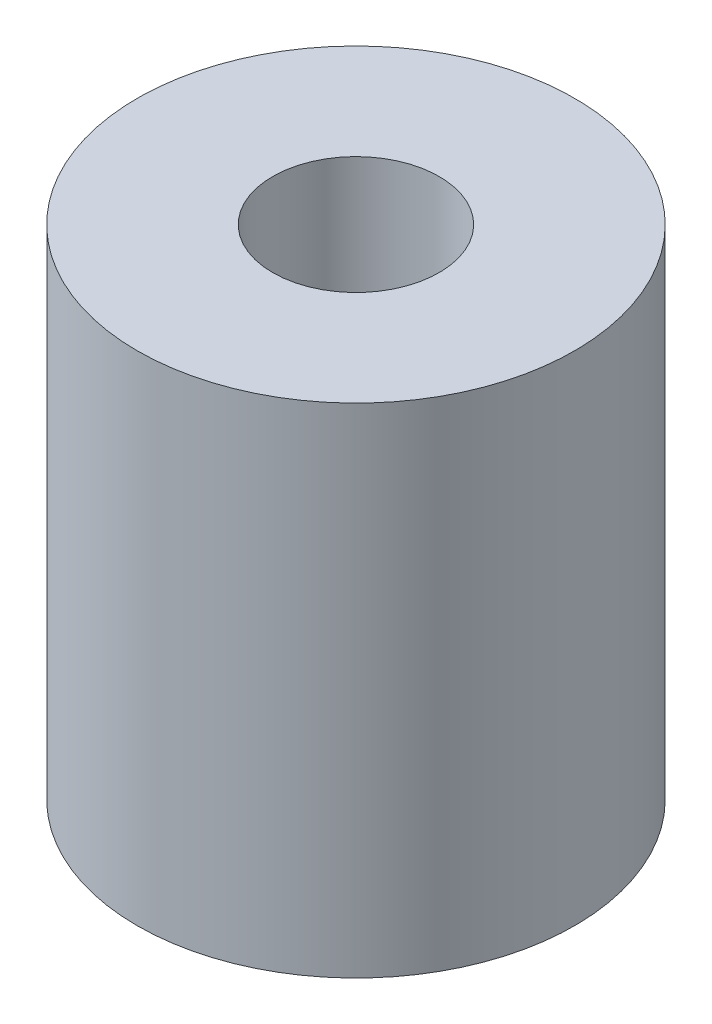
SolidWorks part; units mm, degrees
ref_plane "Front Plane" through (0, 0, 0) normal (0, 0, 1) x (1, 0, 0)
ref_plane "Top Plane" through (0, 0, 0) normal (0, 1, 0) x (1, 0, 0)
ref_plane "Right Plane" through (0, 0, 0) normal (1, 0, 0) x (0, 0, -1)
sketch "Sketch1" plane through (0, 0, 0) normal (0, 1, 0) x (1, 0, 0)
  circle A0 centre (0, 0) radius 13
  circle A1 centre (0, 0) radius 4.95
  dimension "D1" = 26
  dimension "D2" = 9.9
extrude "Boss-Extrude1" add sketch "Sketch1" along normal blind 29.6
ref_plane "Plane1" through (0, 15.1, 0) normal (0, 1, 0) x (1, 0, 0)
sketch "Sketch2" plane through (0, 15.1, 0) normal (0, 1, 0) x (1, 0, 0)
  circle A0 centre (0, 0) radius 4.95
extrude "Boss-Extrude3" add sketch "Sketch2" against normal offset from surface (5.1 mm away) 10 up to face at (0, 0, 13)
sketch "Sketch3" plane through (0, 0, 0) normal (0, -1, 0) x (1, 0, 0)
  circle A1 centre (0, 0) radius 13
  circle A2 centre (0, 0) radius 13
  circle A3 centre (0, 0) radius 3.9
  circle A4 centre (0, 0) radius 4.95 construction
  circle A5 centre (0, 0) radius 4.95
  circle M5 centre (0, 0) radius 4.95
  dimension "D2" = 7.8
  dimension "D1" = 0
extrude "Boss-Extrude4" add sketch "Sketch3" against normal blind 11.85 contours A3 M5 region at (-4.81, 0, 0)
